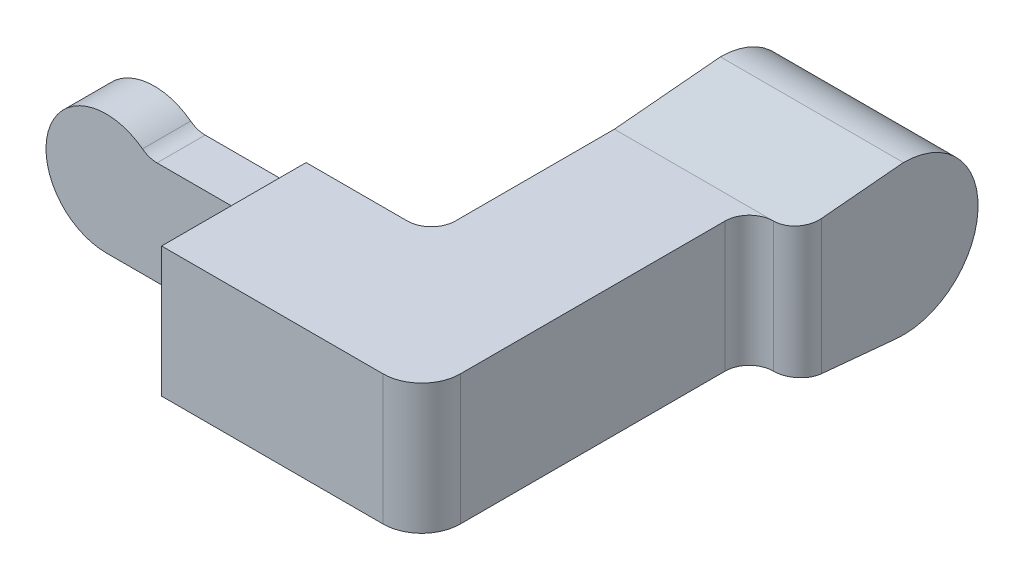
SolidWorks part; units mm, degrees
ref_plane "Front Plane" through (0, 0, 0) normal (0, 0, 1) x (1, 0, 0)
ref_plane "Top Plane" through (0, 0, 0) normal (0, 1, 0) x (1, 0, 0)
ref_plane "Right Plane" through (0, 0, 0) normal (1, 0, 0) x (0, 0, -1)
sketch "Sketch1" plane through (0, 0, 0) normal (0, 1, 0) x (1, 0, 0)
  line L0 (0, 0) -> (46, 0)
  line L1 (54, 8) -> (54, 68)
  line L2 (54, 68) -> (26, 68)
  line L3 (26, 68) -> (26, 35)
  line L4 (21, 30) -> (0, 30)
  line L7 (0, 15) -> (0, 0)
  line L8 (0, 15) -> (0, 30)
  arc A0 (46, 0) -> (54, 8) centre (46, 8) ccw
  arc A1 (21, 30) -> (26, 35) centre (21, 35) ccw
  dimension "D1" = 8
  dimension "D2" = 5
extrude "Boss-Extrude1" add sketch "Sketch1" along normal blind 13.5 and the other way blind 13.5
sketch "Sketch2" plane through (0, 0, 0) normal (0, 0, 1) x (1, 0, 0)
  line L0 (0, -13.5) -> (-31.5, -13.5)
  line L1 (0, -13.5) -> (0, 13.5) construction
  line L2 (0, 7.9621) -> (-20.9497, 7.9621)
  line L3 (0, 7.9621) -> (0, -13.5)
  arc A0 (-23.964, 8.9729) -> (-31.5, -13.5) centre (-31.5, -1) ccw
  arc A1 (-20.9497, 7.9621) -> (-23.964, 8.9729) centre (-20.9497, 12.9621) cw
  dimension "D1" = 31.5
  dimension "D2" = 5
extrude "Boss-Extrude2" add sketch "Sketch2" along normal blind 10 from offset 30 offset against normal yes
fillet "Fillet3" radius 2 2 edges type face fillet first side face at (-7.8561, 7.9621, -23.75) first side face at (-21.5731, -1.5684, -20) second side face at (0, 0.404, -17.5)
ref_plane "Plane1" through (26, 0, 0) normal (-1, 0, 0) x (0, 0, 1)
sketch "Sketch4" plane through (26, 0, 0) normal (-1, 0, 0) x (0, 0, 1)
  line L0 (-88.5492, -15.4319) -> (-68, -13.5)
  line L1 (-68, -13.5) -> (-68, 13.5)
  line L2 (-68, 13.5) -> (-90, 15.5)
  arc A0 (-87.2049, 15.2459) -> (-88.5492, -15.4319) centre (-90, 0) ccw
extrude "Boss-Extrude3" add sketch "Sketch4" against normal blind 38 contours L2 A0 L0 L1 region at (26, -0.0105, -85.6898)
fillet "Fillet4" radius 5 1 edges type face fillet first side face at (54, -3.375, -23) second side face at (61.5, -3.375, -68)
fillet "Fillet5" radius 5 1 edges at (64, 0, -68) type face fillet first side face at (62.75, 0, -68) second side face at (64, -0.173, -82.6894)
ref_point "Point1"
ref_point "Point2"
ref_axis "Axis1" through (-31.5, -1, -30) along (0, 0, 1)
sketch "Sketch6" plane through (0, 0, -20) normal (0, 0, 1) x (1, 0, 0)
  line L0 (-31.5, -1) -> (-18.3284, -1) construction
